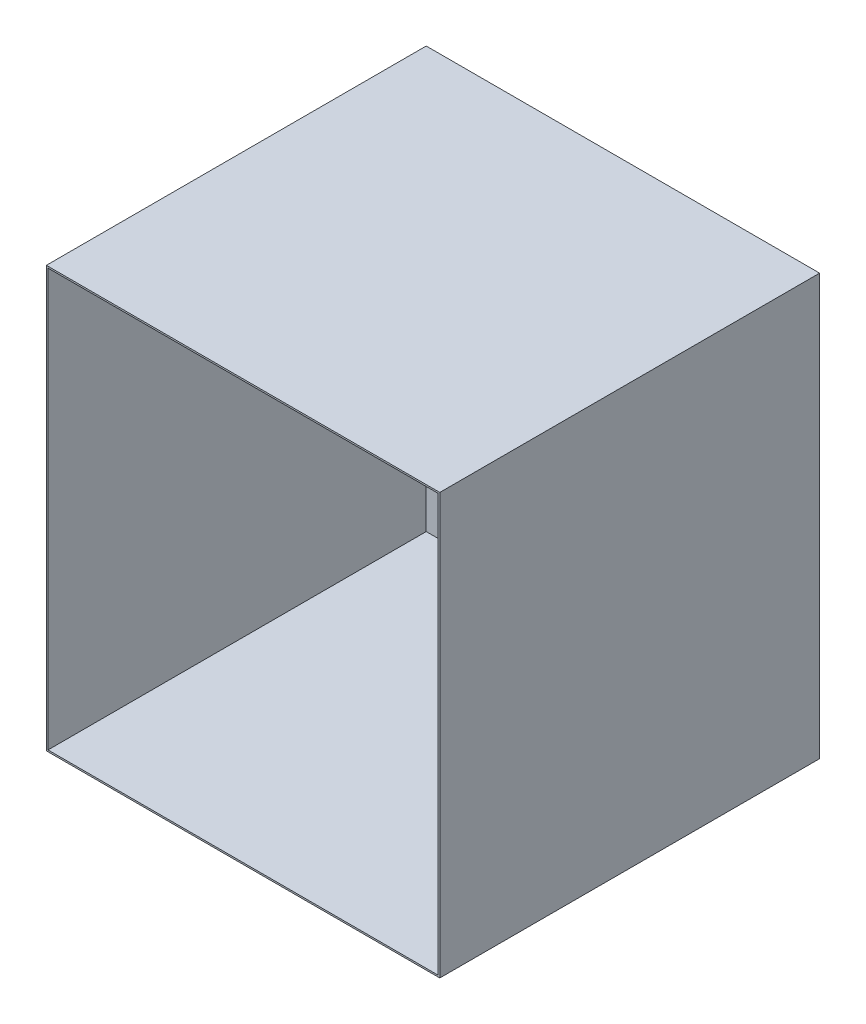
SolidWorks part; units mm, degrees
ref_plane "Plan de face" through (0, 0, 0) normal (0, 0, 1) x (1, 0, 0)
ref_plane "Plan de dessus" through (0, 0, 0) normal (0, 1, 0) x (1, 0, 0)
ref_plane "Plan de droite" through (0, 0, 0) normal (1, 0, 0) x (0, 0, -1)
sketch "Esquisse1" plane through (0, 0, 0) normal (0, 0, 1) x (1, 0, 0)
  line L0 (-143.8, -153.8) -> (-143.8, 153.8)
  line L1 (-145, -155) -> (145, -155)
  line L2 (-145, -155) -> (-145, 155)
  line L3 (-145, 155) -> (145, 155)
  line L4 (145, -155) -> (145, 155)
  line L5 (-145, -155) -> (145, 155) construction
  line L6 (-145, 155) -> (145, -155) construction
  line L7 (-143.8, 153.8) -> (143.8, 153.8)
  line L8 (143.8, -153.8) -> (143.8, 153.8)
  line L9 (-143.8, -153.8) -> (143.8, -153.8)
  point P0 (0, 0)
  dimension "D2" = 290
  dimension "D3" = 310
  dimension "D1" = 1.2
extrude "Boss.-Extru.1" add sketch "Esquisse1" along normal blind 280
extrude "Boss.-Extru.2" add sketch "Esquisse1<2>" along normal blind 1.2 contours L0 L9 L8 L7 region at (0, 0, 0)
sketch "Esquisse1<2>" plane through (0, 0, 0) normal (0, 0, 1) x (1, 0, 0) same geometry as "Esquisse1"
